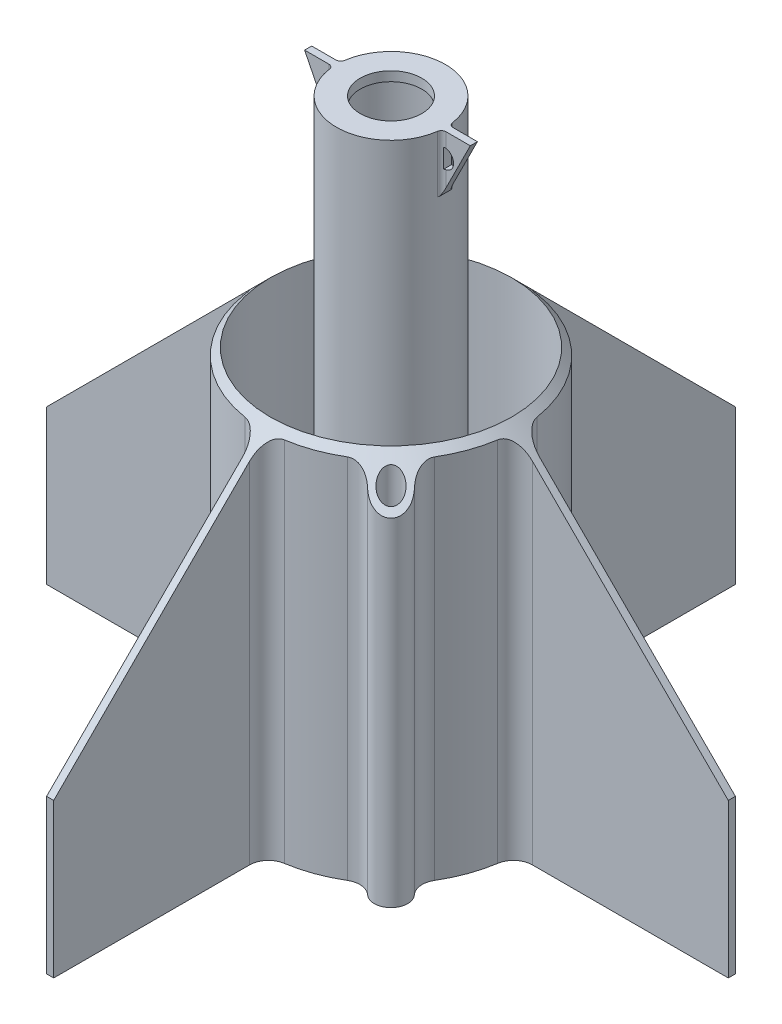
SolidWorks part; units mm, degrees
ref_plane "Front Plane" through (0, 0, 0) normal (0, 0, 1) x (1, 0, 0)
ref_plane "Top Plane" through (0, 0, 0) normal (0, 1, 0) x (1, 0, 0)
ref_plane "Right Plane" through (0, 0, 0) normal (1, 0, 0) x (0, 0, -1)
sketch "Sketch1" plane through (0, 0, 0) normal (0, 0, 1) x (1, 0, 0)
  line L0 (6.5, 125) -> (11.5, 125)
  line L1 (11.5, 125) -> (11.5, 2)
  line L2 (11.5, 2) -> (25.5, 2)
  line L3 (25.5, 2) -> (25.5, 80)
  line L4 (25.5, 80) -> (27, 80)
  line L5 (27, 80) -> (27, 0)
  line L6 (27, 0) -> (10.35, 0)
  line L7 (10.35, 0) -> (10.35, 123)
  line L8 (10.35, 123) -> (6.5, 123)
  line L9 (6.5, 123) -> (6.5, 125)
  line L10 (0, -68.75) -> (0, 68.75) construction
  line L11 (-6.5, 123) -> (-6.5, 125) construction
  line L12 (-10.35, 123) -> (-6.5, 123) construction
  line L13 (-10.35, 0) -> (-10.35, 123) construction
  line L14 (-27, 0) -> (-10.35, 0) construction
  line L15 (-27, 80) -> (-27, 0) construction
  line L16 (-25.5, 80) -> (-27, 80) construction
  line L17 (-25.5, 2) -> (-25.5, 80) construction
  line L18 (-11.5, 2) -> (-25.5, 2) construction
  line L19 (-11.5, 125) -> (-11.5, 2) construction
  line L20 (-6.5, 125) -> (-11.5, 125) construction
  line L21 (0, 0) -> (0, 125) construction
  dimension "D1" = 2
  dimension "D2" = 2
  dimension "D3" = 80
  dimension "D4" = 125
  dimension "D5" = 20.7
  dimension "D6" = 23
  dimension "D7" = 13
  dimension "D8" = 51
  dimension "D9" = 54
revolve "Revolve2" add sketch "Sketch1" angle 360 about L21
sketch "Sketch3" plane through (0, 0, 0) normal (1, 0, 0) x (0, 0, -1)
  line L0 (-27, 80) -> (-27, 0) construction
  line L1 (-26, 80) -> (-26, 0) construction
  line L2 (25.5, 80) -> (-25.5, 80) construction
  line L3 (-27, 80) -> (-72, 80)
  line L4 (27, 80) -> (-27, 80) construction
  line L5 (-72, 80) -> (-72, 0)
  line L6 (-72, 0) -> (-26, 0)
  line L7 (-27, 80) -> (-26, 80)
  line L8 (-26, 80) -> (-26, 0)
  dimension "D1" = 1
  dimension "D3" = 45
extrude "Boss-Extrude1" add sketch "Sketch3" along normal mid plane 1.5
pattern_circular "CirPattern1" count 4 over 360 about axis through (0, 0, 0) along (0, -1, 0) of "Boss-Extrude1"
sketch "Sketch4" plane through (0, 0, 0) normal (0, 0, 1) x (1, 0, 0)
  line L0 (11.5, 125) -> (11.5, 80) construction
  line L1 (26.9896, 80) -> (0.75, 80) construction
  line L2 (11.5, 2) -> (11.5, 125) construction
  line L3 (10.5, 125) -> (10.5, 80) construction
  line L4 (11.5, 125) -> (-11.5, 125) construction
  line L5 (11.5, 125) -> (17.5, 125)
  line L6 (17.5, 125) -> (11.5, 113)
  line L7 (11.5, 113) -> (10.5, 113)
  line L8 (10.5, 113) -> (10.5, 125)
  line L9 (10.5, 125) -> (11.5, 125)
  dimension "D1" = 1
  dimension "D2" = 6
  dimension "D3" = 12
extrude "Boss-Extrude2" add sketch "Sketch4" along normal mid plane 1.5
sketch "Sketch5" plane through (0, 0, 0.75) normal (0, 0, 1) x (1, 0, 0)
  line L0 (11.9755, 125) -> (11.9755, 113.951) construction
  line L1 (17.5, 125) -> (11.4755, 125) construction
  line L2 (11.5, 113) -> (17.5, 125) construction
  line L3 (11.4755, 125) -> (11.4755, 113) construction
  line L4 (11.9755, 122) -> (11.9755, 118)
  arc A0 (11.9755, 122) -> (11.9755, 118) centre (11.9755, 120) cw
  dimension "D2" = 180
  dimension "D3" = 2
  dimension "D1" = 0.5
  dimension "D4" = 3
extrude "Cut-Extrude2" cut sketch "Sketch5" against normal through all both and the other way through all
mirror "Mirror1" about plane through (0, 0, 0) normal (1, 0, 0) of "Cut-Extrude2", "Boss-Extrude2"
sketch "Sketch7" plane through (0, 0, 0) normal (0, 1, 0) x (1, 0, 0)
  line L0 (0, 0) -> (30.7111, 30.7111) construction
  line L1 (0, 0) -> (72.9642, 0) construction
  dimension "D1" = 45
ref_plane "Plane_direction_guidance" through (0, 0, 0) normal (0.7071, 0, 0.7071) x (0.7071, 0, -0.7071)
sketch "Sketch8" plane through (0, 0, 0) normal (0, 1, 0) x (1, 0, 0)
  line L0 (0, 0) -> (35.9359, -35.9359) construction
  line L1 (72, -0.75) -> (26.9896, -0.75) construction
  line L2 (1.744, -36.4398) -> (38.2738, 0.09) construction
  line L3 (-5.3582, -42.1278) -> (40.669, 3.8995) construction
  line L4 (15.9099, -20.8597) -> (18.5616, -23.5113)
  line L5 (15.9099, -20.8597) -> (20.8597, -15.9099)
  line L6 (23.5113, -18.5616) -> (20.8597, -15.9099)
  line L7 (18.5616, -23.5113) -> (23.5113, -18.5616) construction
  line L8 (15.7896, -23.1013) -> (23.8905, -15.0004) construction
  arc A0 (0.75, -26.9896) -> (26.9896, -0.75) centre (0, 0) ccw construction
  arc A1 (18.5616, -23.5113) -> (23.5113, -18.5616) centre (21.0364, -21.0364) ccw
  circle A2 centre (21.0364, -21.0364) radius 2.25 construction
  point P14 (18.3848, -18.3848)
  dimension "D3" = 180
  dimension "D4" = 7
  dimension "D5" = 4.5
  dimension "D1" = 45
  dimension "D2" = 1
  dimension "D6" = 0.5
extrude "Boss-Extrude3" add sketch "Sketch8" along normal up to surface (80 mm away)
sketch "Sketch9" plane through (0, 0, 0) normal (0, -1, 0) x (1, 0, 0)
  circle A0 centre (21.0364, 21.0364) radius 2.25
  dimension "D1" = 4.5
extrude "Cut-Extrude3" cut sketch "Sketch9" against normal through all both and the other way through all
mirror "Mirror2" about plane through (0, 0, 0) normal (0.7071, 0, 0.7071) of "Boss-Extrude3", "Cut-Extrude3"
sketch "Sketch10" plane through (0, 0, 0) normal (0, 0, 1) x (1, 0, 0)
  line L0 (24.9896, 98.8616) -> (24.9896, -7.2473) construction
  line L1 (77, 98.8616) -> (77, -16.5651) construction
  line L2 (72, 80) -> (72, 0) construction
  line L3 (26.9896, 80) -> (26.9896, 0) construction
  line L4 (24.9896, 85) -> (77, 85)
  line L5 (77, 85) -> (77, 27.4896)
  line L6 (77, 27.4896) -> (24.9896, 79.5)
  line L7 (24.9896, 79.5) -> (24.9896, 85)
  line L8 (26.9896, 80) -> (72, 80) construction
  line L9 (26.9896, 80) -> (21.4057, 80) construction
  line L10 (0, 125) -> (0, 0) construction
  line L11 (11.4755, 125) -> (-11.4755, 125) construction
  dimension "D1" = 5
  dimension "D2" = 2
  dimension "D3" = 5
  dimension "D4" = 0.5
  dimension "D5" = 45
revolve "Cut-Revolve1" cut sketch "Sketch10" angle 360 about L10
fillet "Fillet2" radius 4 12 edges at (-0.75, 38.7448, 26.9896) (0.75, 38.7448, 26.9896) (26.9896, 38.7448, 0.75) (0.75, 38.7448, -26.9896) (-26.9896, 38.7448, 0.75) (-26.9896, 38.7448, -0.75) (-0.75, 38.7448, -26.9896) (-16.4559, 38.7448, -21.4057) (26.9896, 38.7448, -0.75) (16.4559, 38.7448, 21.4057) (21.4057, 38.7448, 16.4559) (-21.4057, 38.7448, -16.4559)
fillet "Fillet3" radius 6 1 edges at (0, 2, -25.5)
fillet "Fillet4" radius 6 1 edges at (0, 2, -11.5)
fillet "Fillet8" radius 1 4 edges at (11.4755, 119, 0.75) (11.4755, 119, -0.75) (-11.4755, 119, 0.75) (-11.4755, 119, -0.75)
